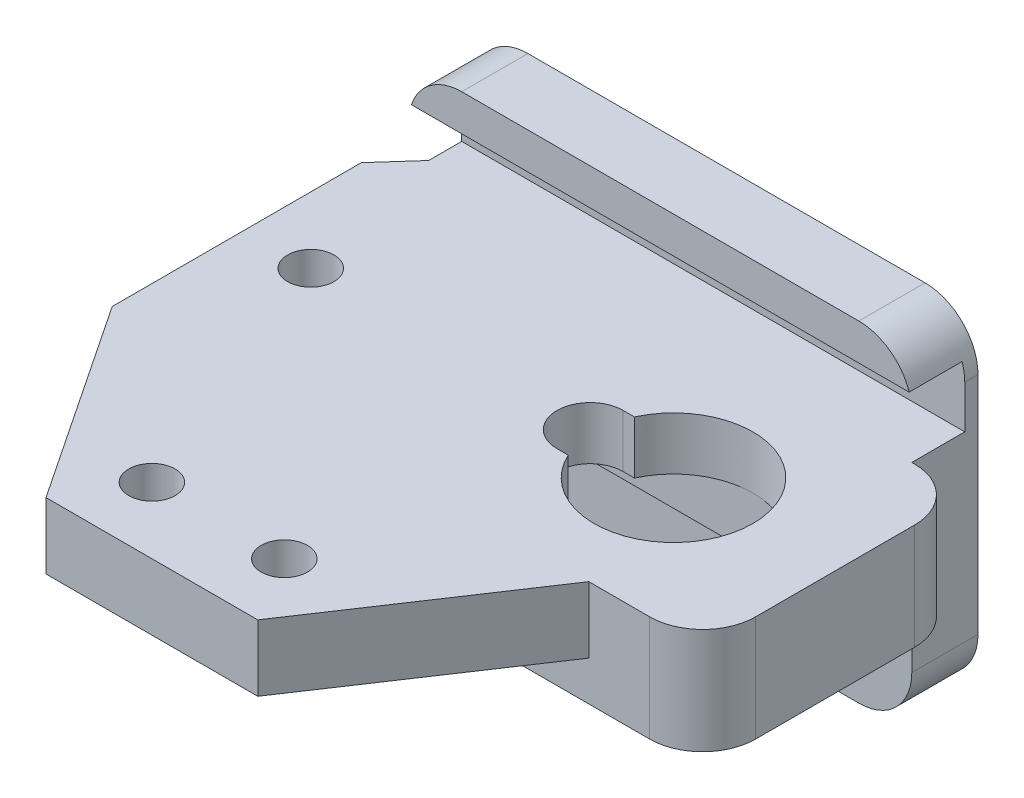
SolidWorks part; units mm, degrees
ref_plane "Front Plane" through (0, 0, 0) normal (0, 0, 1) x (1, 0, 0)
ref_plane "Top Plane" through (0, 0, 0) normal (0, 1, 0) x (1, 0, 0)
ref_plane "Right Plane" through (0, 0, 0) normal (1, 0, 0) x (0, 0, -1)
sketch "Sketch1" plane through (0, 0, 0) normal (0, 1, 0) x (1, 0, 0)
  line L0 (0, 15) -> (0, 33.8197)
  line L1 (10, 45) -> (26, 45)
  line L2 (26, 45) -> (36, 35)
  line L3 (36, 35) -> (60, 35)
  line L4 (60, 35) -> (60, 15)
  line L5 (60, 15) -> (36, 15)
  line L6 (36, 15) -> (26, 0)
  line L7 (26, 0) -> (10, 0)
  line L8 (10, 0) -> (0, 15)
  line L9 (10, 45) -> (0, 33.8197)
  circle A0 centre (5, 25) radius 1.75
  circle A1 centre (13, 5) radius 1.75
  circle A2 centre (23, 5) radius 1.75
  point P18 (0, 0)
  point P19 (0, 0)
  point P20 (23.7496, 1.4044)
  dimension "D13" = 3.5
  dimension "D14" = 3.5
  dimension "D20" = 25
  dimension "D1" = 60
  dimension "D2" = 20
  dimension "D3" = 10
  dimension "D4" = 15
  dimension "D5" = 15
  dimension "D6" = 45
  dimension "D7" = 16
  dimension "D8" = 10
  dimension "D9" = 10
  dimension "D10" = 10
  dimension "D11" = 16
  dimension "D12" = 10
  dimension "D15" = 5
  dimension "D16" = 10
  dimension "D17" = 5
  dimension "D18" = 3
  dimension "D19" = 3
extrude "Boss-Extrude1" add sketch "Sketch1" along normal blind 5
sketch "Sketch2" plane through (0, 0, 0) normal (0, -1, 0) x (1, 0, 0)
  line L0 (36, -15) -> (60, -15) construction
  line L1 (9.6, -35) -> (44.6, -35)
  line L2 (9.6, -35) -> (9.6, -15)
  line L3 (9.6, -15) -> (44.6, -15)
  line L4 (44.6, -35) -> (44.6, -15)
  line L5 (9.6, -35) -> (44.6, -15) construction
  line L6 (9.6, -15) -> (44.6, -35) construction
  line L7 (60, -15) -> (60, -35) construction
  line L8 (15.8, -31) -> (38.4, -31)
  line L9 (15.8, -31) -> (15.8, -19)
  line L10 (15.8, -19) -> (38.4, -19)
  line L11 (38.4, -31) -> (38.4, -19)
  line L12 (15.8, -31) -> (38.4, -19) construction
  line L13 (15.8, -19) -> (38.4, -31) construction
  point P0 (27.1, -25)
  point P7 (27.1, -25)
  dimension "D1" = 22.6
  dimension "D2" = 6.2
  dimension "D3" = 4
  dimension "D4" = 12
  dimension "D5" = 15.4
extrude "Boss-Extrude2" add sketch "Sketch2" along normal blind 3
sketch "Sketch3" plane through (0, 0, 0) normal (0, -1, 0) x (1, 0, 0)
  line L4 (44.6, -15) -> (44.6, -35)
  line L5 (44.6, -35) -> (60, -35)
  line L6 (60, -35) -> (60, -15)
  line L7 (60, -15) -> (44.6, -15)
  line L8 (44.6, -15) -> (44.6, -35)
  line L9 (44.6, -35) -> (60, -35)
  line L10 (60, -35) -> (60, -15)
  line L11 (60, -15) -> (44.6, -15)
  dimension "D1" = 0
extrude "Cut-Extrude1" cut sketch "Sketch3" against normal through all
sketch "Sketch4" plane through (0, -3, 0) normal (0, -1, 0) x (1, 0, 0)
  line L0 (15.8, -19) -> (15.8, -31) construction
  line L1 (15.8, -19) -> (15.8, -31) construction
  circle A0 centre (13.52, -25) radius 1
  circle A1 centre (40.67, -25) radius 1
  point P8 (15.8, -25)
  point P9 (0, 0)
  dimension "D1" = 2
  dimension "D2" = 2
  dimension "D3" = 2.28
  dimension "D4" = 27.15
extrude "Cut-Extrude2" cut sketch "Sketch4" against normal blind 7
sketch "Sketch5" plane through (0, 0, -35) normal (0, 0, -1) x (-1, 0, 0)
  line L0 (-36, 5) -> (-26, 5) construction
  line L1 (-40.4, 12.25) -> (-2.4, 12.25)
  line L2 (-40.4, 12.25) -> (-40.4, -12.75)
  line L3 (-40.4, -12.75) -> (-2.4, -12.75)
  line L4 (-2.4, 12.25) -> (-2.4, -12.75)
  line L5 (0, 5) -> (0, 0) construction
  dimension "D1" = 38
  dimension "D2" = 25
  dimension "D3" = 7.25
  dimension "D4" = 2.4
extrude "Boss-Extrude3" add sketch "Sketch5" along normal blind 5
sketch "Sketch6" plane through (0, 0, -40) normal (0, 0, -1) x (-1, 0, 0)
  line L2 (-40.4, -12.75) -> (-2.4, -12.75) construction
  circle A0 centre (-21.3985, -0.25) radius 2.3
  point P4 (0, 0)
  dimension "D1" = 4.6
  dimension "D2" = 12.5
  dimension "D3" = 21.4
extrude "Cut-Extrude3" cut sketch "Sketch6" against normal blind 4
fillet "Fillet1" radius 4 6 edges at (2.4, -12.75, -37.5) (2.4, 12.25, -37.5) (40.4, 12.25, -37.5) (40.4, -12.75, -37.5) (44.6, 1, -35) (44.6, 1, -15)
extrude "Cut-Extrude4" cut sketch "Sketch2<2>" against normal blind 1 contours L8 L11 L10 L9 region at (27.1, 0, -25)
sketch "Sketch2<2>" plane through (0, 0, 0) normal (0, -1, 0) x (1, 0, 0) same geometry as "Sketch2"
sketch "Sketch7" plane through (0, 1, 0) normal (0, -1, 0) x (1, 0, 0)
  line L0 (15.8, -31) -> (38.4, -31) construction
  line L2 (38.4, -19) -> (15.8, -19) construction
  line L3 (38.4, -31) -> (38.4, -19) construction
  line L4 (26.1, -22.5) -> (26.9456, -22.5)
  line L5 (26.1, -27.5) -> (26.9456, -27.5)
  arc A0 (26.9456, -27.5) -> (26.9456, -22.5) centre (32.4, -25) ccw
  arc A1 (26.1, -22.5) -> (26.1, -27.5) centre (26.1, -25) ccw
  point P14 (0, 0)
  dimension "D1" = 5
  dimension "D2" = 6.3
extrude "Cut-Extrude5" cut sketch "Sketch7" against normal through all
sketch "Sketch8" plane through (0, 0, 0) normal (0, -1, 0) x (1, 0, 0)
  line L6 (26, -45) -> (31, -40)
  line L7 (31, -40) -> (23.6849, -40)
  line L8 (23.6849, -40) -> (19.1122, -40)
  line L9 (19.1122, -40) -> (5.5279, -40)
  line L10 (5.5279, -40) -> (10, -45)
  line L11 (10, -45) -> (26, -45)
  line L12 (26, -45) -> (31, -40)
  line L13 (31, -40) -> (23.6849, -40)
  line L14 (23.6849, -40) -> (19.1122, -40)
  line L15 (19.1122, -40) -> (5.5279, -40)
  line L16 (5.5279, -40) -> (10, -45)
  line L17 (10, -45) -> (26, -45)
  dimension "D1" = 0
extrude "Cut-Extrude6" cut sketch "Sketch8" against normal through all
sketch "Sketch9" plane through (0, 0, -35) normal (0, 0, 1) x (1, 0, 0)
  line L1 (2.4, 5) -> (40.4, 5)
  line L2 (2.4, 5) -> (2.4, 9.5)
  line L3 (2.4, 9.5) -> (40.4, 9.5)
  line L4 (40.4, 5) -> (40.4, 9.5)
  point P5 (0, 0)
  point P8 (0, 0)
  dimension "D1" = 4.5
extrude "Cut-Extrude7" cut sketch "Sketch9" against normal blind 4
